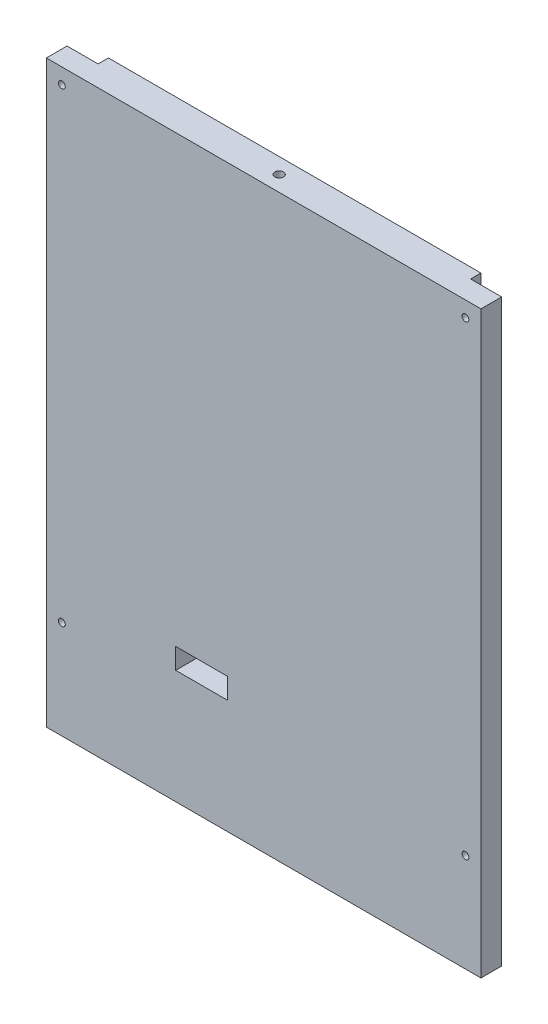
SolidWorks part; units mm, degrees
ref_plane "Front Plane" through (0, 0, 0) normal (0, 0, 1) x (1, 0, 0)
ref_plane "Top Plane" through (0, 0, 0) normal (0, 1, 0) x (1, 0, 0)
ref_plane "Right Plane" through (0, 0, 0) normal (1, 0, 0) x (0, 0, -1)
sketch "Sketch3" plane through (0, 0, 0) normal (0, 1, 0) x (1, 0, 0)
  line L0 (-105, 0) -> (105, 0)
  line L1 (105, 0) -> (105, -10)
  line L2 (105, -10) -> (-105, -10)
  line L3 (-105, -10) -> (-105, 0)
  dimension "D1" = 210
  dimension "D2" = 10
extrude "Boss-Extrude1" add sketch "Sketch3" along normal blind 240
ref_plane "Plane1" through (0, 35, 0) normal (0, 1, 0) x (1, 0, 0)
sketch "Sketch5" plane through (0, 240, 0) normal (0, 1, 0) x (1, 0, 0)
  line L0 (-90, 0) -> (-90, 5)
  line L1 (105, 0) -> (-105, 0) construction
  line L2 (-90, 5) -> (90, 5)
  line L3 (90, 5) -> (90, 0)
  line L4 (-105, 0) -> (-105, -10) construction
  line L5 (105, 0) -> (90, 0)
  line L9 (-105, 0) -> (-105, -10)
  line L10 (-105, -10) -> (105, -10)
  line L11 (105, -10) -> (105, 0)
  line L12 (105, 0) -> (-105, 0)
  line L13 (-105, 0) -> (-105, -10)
  line L14 (-105, -10) -> (105, -10)
  line L15 (105, -10) -> (105, 0)
  line L16 (-90, 0) -> (-105, 0)
  dimension "D1" = 180
  dimension "D2" = 5
  dimension "D3" = 15
  dimension "D4" = 0
extrude "Boss-Extrude2" add sketch "Sketch5" against normal up to surface (205 mm away) up to plane "Plane1"
sketch "Sketch6" plane through (0, 35, 0) normal (0, 1, 0) x (1, 0, 0)
  line L0 (-22.5, 0) -> (-22.5, 15)
  line L2 (-22.5, 15) -> (22.5, 15)
  line L3 (22.5, 15) -> (22.5, 0)
  line L4 (22.5, 0) -> (-22.5, 0)
  line L6 (90, 5) -> (-90, 5) construction
  dimension "D1" = 45
  dimension "D2" = 10
extrude "Boss-Extrude3" add sketch "Sketch6" against normal blind 10
sketch "Sketch7" plane through (0, 0, 10) normal (0, 0, 1) x (1, 0, 0)
  line L0 (0, -1000) -> (0, 49000) construction
  line L1 (-105, 240) -> (105, 240) construction
  line L2 (-105, 240) -> (-105, 0) construction
  line L3 (8.25, 0) -> (-8.25, 0) construction
  circle A0 centre (-97.5, 232.5) radius 1.65
  circle A1 centre (-97.5, 7.5) radius 1.65
  circle A2 centre (97.5, 7.5) radius 1.65
  circle A3 centre (97.5, 232.5) radius 1.65
  dimension "D1" = 3.3
  dimension "D2" = 7.5
  dimension "D4" = 7.5
  dimension "D3" = 7.5
  dimension "D5" = 7.5
extrude "Cut-Extrude1" cut sketch "Sketch7" against normal up to surface (10 mm away) up to face at (0, 95.8333, 0)
sketch "Sketch8" plane through (0, 0, 10) normal (0, 0, 1) x (1, 0, 0)
  line L0 (-105, 240) -> (-105, 0) construction
  line L1 (-42.5, 25) -> (-17.5, 25)
  line L2 (-42.5, 25) -> (-42.5, 15)
  line L3 (-42.5, 15) -> (-17.5, 15)
  line L4 (-17.5, 25) -> (-17.5, 15)
  line L5 (-105, 0) -> (105, 0) construction
  line L6 (0, -1000) -> (0, 49000) construction
  line L7 (42.5, 15) -> (17.5, 15)
  line L8 (17.5, 25) -> (17.5, 15)
  line L9 (42.5, 25) -> (17.5, 25)
  line L10 (42.5, 25) -> (42.5, 15)
  dimension "D1" = 62.5
  dimension "D2" = 15
  dimension "D3" = 25
  dimension "D4" = 10
extrude "Cut-Extrude2" cut sketch "Sketch8" against normal up to surface (10 mm away) contours L4 L1 L2 L3 region at (-30, 20, 10) up to face at (99.15, 232.5, 0)
sketch "Sketch9" plane through (0, 0, 0) normal (0, -1, 0) x (1, 0, 0)
  line L4 (-105, 10) -> (-105, 0)
  line L5 (-105, 0) -> (105, 0)
  line L6 (105, 0) -> (105, 10)
  line L7 (105, 10) -> (-105, 10)
  line L8 (-105, 10) -> (-105, 0)
  line L9 (-105, 0) -> (105, 0)
  line L10 (105, 0) -> (105, 10)
  line L11 (105, 10) -> (-105, 10)
  dimension "D1" = 0
extrude "Boss-Extrude4" add sketch "Sketch9" along normal blind 40
sketch "Sketch10" plane through (0, 240, 0) normal (0, 1, 0) x (1, 0, 0)
  line L0 (-105, -10) -> (105, -10) construction
  circle A0 centre (0, -2.5) radius 2.1
  point P5 (0, 0)
  dimension "D1" = 4.2
  dimension "D2" = 7.5
extrude "Cut-Extrude3" cut sketch "Sketch10" against normal blind 4.5
